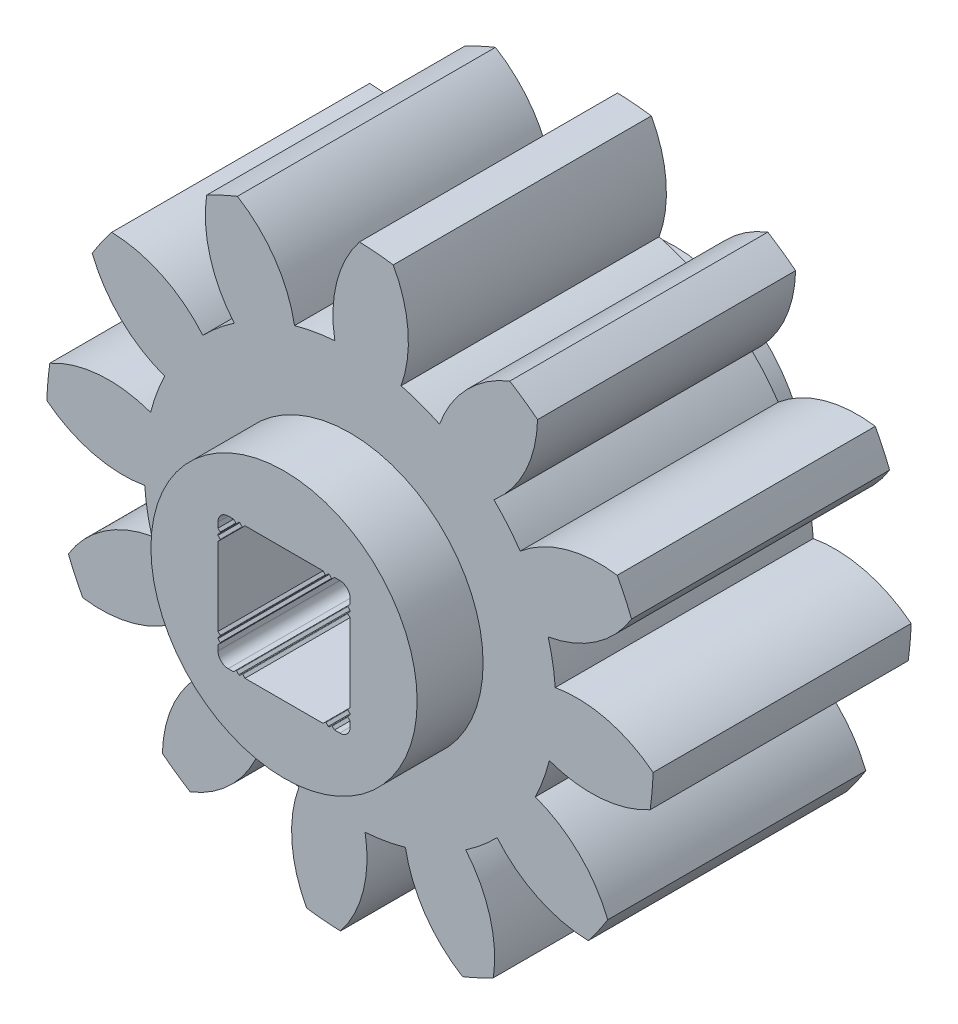
SolidWorks part; units mm, degrees
material "ABS PC"
ref_plane "Front Plane" through (0, 0, 0) normal (0, 0, 1) x (1, 0, 0)
ref_plane "Top Plane" through (0, 0, 0) normal (0, 1, 0) x (1, 0, 0)
ref_plane "Right Plane" through (0, 0, 0) normal (1, 0, 0) x (0, 0, -1)
sketch "Sketch1" plane through (0, 0, 0) normal (0, 0, 1) x (1, 0, 0)
  circle A0 centre (0, 0) radius 3.25
  dimension "D1" = 6.5
extrude "Extrude1" add sketch "Sketch1" along normal mid plane 9.52
sketch "Sketch2" plane through (0, 0, 0) normal (0, 0, 1) x (1, 0, 0)
  circle A0 centre (0, 0) radius 5.025
  dimension "D1" = 10.05
extrude "Extrude2" add sketch "Sketch2" along normal mid plane 6.3
sketch "Sketch3" plane through (0, 0, 0) normal (0, 0, 1) x (1, 0, 0)
  line L0 (-0.3692, 5.0114) -> (-0.3692, 4.4848)
  line L1 (1.2472, 4.8678) -> (1.0679, 4.3715)
  line L2 (0, 0) -> (0, 7.0627) construction
  arc A0 (1.0679, 4.3715) -> (-0.3692, 4.4848) centre (0, 0) ccw
  circle A2 centre (0, 0) radius 5.025 construction
  arc A11 (0.2316, 7.4004) -> (-0.3692, 5.0114) centre (2.5841, 5.5388) ccw
  arc A12 (1.057, 7.3282) -> (0.2316, 7.4004) centre (0, 0) ccw
  arc A13 (1.2472, 4.8678) -> (1.057, 7.3282) centre (-1.5743, 5.8872) ccw
  point P13 (0, 0)
  dimension "D2" = 7.0627
  dimension "D3" = 4.5
  dimension "D4" = 0.3692
  dimension "D5" = 3
  dimension "D6" = 3
  dimension "D7" = 1.0679
  dimension "D9" = 0.8254
  dimension "D11" = 1.6164
  dimension "D14" = 2.389
extrude "Extrude3" add sketch "Sketch3" against normal mid plane 6.3
pattern_circular "CirPattern5" count 12 over 360 about axis through (0, 0, 3.15) along (0, 0, -1) of "Extrude3"
sketch "Sketch4" plane through (0, 0, 4.76) normal (0, 0, 1) x (1, 0, 0)
  line L0 (0, 0) -> (0, 1.6125) construction
  line L1 (1.6125, 0.9521) -> (1.6125, -0.9521)
  line L2 (1.5578, 1.1595) -> (1.6126, 1.1046)
  line L3 (1.6126, 1.1046) -> (1.6126, 1.0792)
  line L4 (1.6126, 1.0792) -> (1.5577, 1.0245)
  line L5 (1.5579, 1.0071) -> (1.6125, 0.9521)
  line L6 (0.9521, 1.6125) -> (1.0068, 1.5582)
  line L7 (1.0251, 1.558) -> (1.0796, 1.6125)
  line L8 (1.0796, 1.6125) -> (1.105, 1.6125)
  line L9 (1.105, 1.6125) -> (1.1594, 1.558)
  line L10 (1.1775, 1.5581) -> (1.2316, 1.613)
  line L11 (1.6126, 1.2315) -> (1.5578, 1.1774)
  line L12 (1.2316, 1.613) -> (1.6126, 1.613)
  line L13 (1.6126, 1.2315) -> (1.6126, 1.613)
  line L14 (-1.6125, 0) -> (1.6125, 0) construction
  line L15 (-1.5578, -1.1595) -> (-1.6126, -1.1046)
  line L16 (-1.6126, -1.1046) -> (-1.6126, -1.0792)
  line L17 (-1.6126, -1.0792) -> (-1.5577, -1.0245)
  line L18 (-1.5579, -1.0071) -> (-1.6125, -0.9521)
  line L19 (0.9521, -1.6125) -> (-0.9521, -1.6125)
  line L20 (-0.9521, -1.6125) -> (-1.0068, -1.5582)
  line L21 (-1.0251, -1.558) -> (-1.0796, -1.6125)
  line L22 (-1.0796, -1.6125) -> (-1.105, -1.6125)
  line L23 (-1.105, -1.6125) -> (-1.1594, -1.558)
  line L24 (-1.1775, -1.5581) -> (-1.2316, -1.613)
  line L25 (-1.6126, -1.2315) -> (-1.5578, -1.1774)
  line L26 (-1.2316, -1.613) -> (-1.6126, -1.613)
  line L27 (-1.6126, -1.2315) -> (-1.6126, -1.613)
  line L28 (1.6126, -1.2315) -> (1.6126, -1.613)
  line L29 (1.2316, -1.613) -> (1.6126, -1.613)
  line L30 (1.6126, -1.2315) -> (1.5578, -1.1774)
  line L31 (1.1775, -1.5581) -> (1.2316, -1.613)
  line L32 (1.105, -1.6125) -> (1.1594, -1.558)
  line L33 (1.0796, -1.6125) -> (1.105, -1.6125)
  line L34 (1.0251, -1.558) -> (1.0796, -1.6125)
  line L35 (0.9521, -1.6125) -> (1.0068, -1.5582)
  line L36 (1.5579, -1.0071) -> (1.6125, -0.9521)
  line L37 (1.6126, -1.0792) -> (1.5577, -1.0245)
  line L38 (1.6126, -1.1046) -> (1.6126, -1.0792)
  line L39 (1.5578, -1.1595) -> (1.6126, -1.1046)
  line L40 (-1.6126, 1.2315) -> (-1.6126, 1.613)
  line L41 (-1.2316, 1.613) -> (-1.6126, 1.613)
  line L104 (-1.6126, 1.2315) -> (-1.5578, 1.1774)
  line L107 (-1.1775, 1.5581) -> (-1.2316, 1.613)
  line L108 (-1.105, 1.6125) -> (-1.1594, 1.558)
  line L109 (-1.0796, 1.6125) -> (-1.105, 1.6125)
  line L110 (-1.0251, 1.558) -> (-1.0796, 1.6125)
  line L111 (-0.9521, 1.6125) -> (-1.0068, 1.5582)
  line L112 (0.9521, 1.6125) -> (-0.9521, 1.6125)
  line L151 (-1.6125, 0.9521) -> (-1.6125, -0.9521)
  line L152 (-1.5579, 1.0071) -> (-1.6125, 0.9521)
  line L153 (-1.6126, 1.0792) -> (-1.5577, 1.0245)
  line L154 (-1.6126, 1.1046) -> (-1.6126, 1.0792)
  line L155 (-1.5578, 1.1595) -> (-1.6126, 1.1046)
  arc A0 (1.5578, 1.1595) -> (1.5578, 1.1774) centre (1.5845, 1.1684) cw
  arc A1 (1.5579, 1.0071) -> (1.5577, 1.0245) centre (1.5664, 1.0159) cw
  arc A2 (1.0251, 1.558) -> (1.0068, 1.5582) centre (1.016, 1.567) cw
  arc A3 (1.1775, 1.5581) -> (1.1594, 1.558) centre (1.1685, 1.567) cw
  arc A4 (-1.5578, -1.1595) -> (-1.5578, -1.1774) centre (-1.5845, -1.1684) cw
  arc A5 (-1.5579, -1.0071) -> (-1.5577, -1.0245) centre (-1.5664, -1.0159) cw
  arc A6 (-1.0251, -1.558) -> (-1.0068, -1.5582) centre (-1.016, -1.567) cw
  arc A7 (-1.1775, -1.5581) -> (-1.1594, -1.558) centre (-1.1685, -1.567) cw
  arc A8 (1.1775, -1.5581) -> (1.1594, -1.558) centre (1.1685, -1.567) ccw
  arc A9 (1.0251, -1.558) -> (1.0068, -1.5582) centre (1.016, -1.567) ccw
  arc A10 (1.5579, -1.0071) -> (1.5577, -1.0245) centre (1.5664, -1.0159) ccw
  arc A11 (1.5578, -1.1595) -> (1.5578, -1.1774) centre (1.5845, -1.1684) ccw
  arc A55 (-1.1775, 1.5581) -> (-1.1594, 1.558) centre (-1.1685, 1.567) ccw
  arc A56 (-1.0251, 1.558) -> (-1.0068, 1.5582) centre (-1.016, 1.567) ccw
  arc A72 (-1.5579, 1.0071) -> (-1.5577, 1.0245) centre (-1.5664, 1.0159) ccw
  arc A73 (-1.5578, 1.1595) -> (-1.5578, 1.1774) centre (-1.5845, 1.1684) ccw
  point P13 (0, 0)
  dimension "D29" = 0.0128
  dimension "D33" = 0.0123
  dimension "D4" = 1.6125
  dimension "D5" = 1.6125
  dimension "D6" = 1.6125
  dimension "D7" = 0.9521
  dimension "D8" = 0.9521
  dimension "D9" = 0.381
  dimension "D11" = 0.2794
  dimension "D13" = 0.0254
  dimension "D14" = 0.0771
  dimension "D15" = 0.0775
  dimension "D16" = 0.0179
  dimension "D17" = 0.0173
  dimension "D18" = 0.1269
  dimension "D19" = 0.1271
  dimension "D20" = 0.135
  dimension "D22" = 0.2795
  dimension "D23" = 0.1525
  dimension "D26" = 0.0254
  dimension "D27" = 0.0455
  dimension "D28" = 0.0455
  dimension "D30" = 0.1275
  dimension "D31" = 0.1344
extrude "Cut-Extrude1" cut sketch "Sketch4" against normal up to surface (9.52 mm away) up to face at (3.25, 0, -4.76)
fillet "Fillet1" radius 0.25 4 edges at (-1.6126, -1.613, 0) (1.6126, -1.613, 0) (1.6126, 1.613, 0) (-1.6126, 1.613, 0)
ref_axis "Axis1" through (0, 0, 4.76) along (0, 0, -1)
